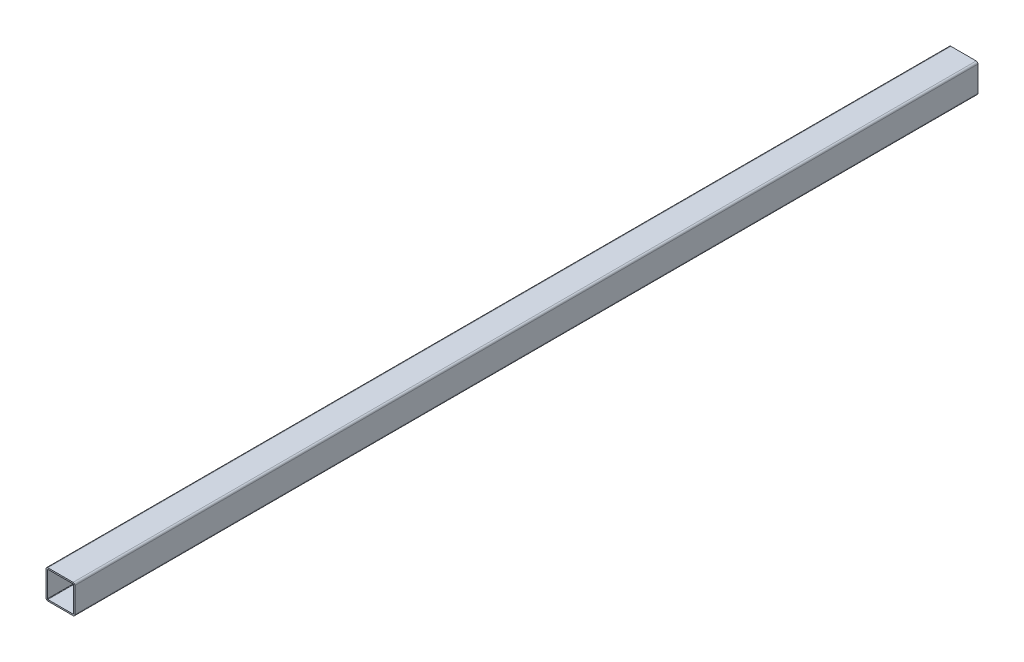
SolidWorks part; units mm, degrees
material "AISI 1010 Steel, hot rolled bar"
ref_plane "Front Plane" through (0, 0, 0) normal (0, 0, 1) x (1, 0, 0)
ref_plane "Top Plane" through (0, 0, 0) normal (0, 1, 0) x (1, 0, 0)
ref_plane "Right Plane" through (0, 0, 0) normal (1, 0, 0) x (0, 0, -1)
sketch "Sketch1" plane through (0, 0, 0) normal (0, 0, 1) x (1, 0, 0)
  line L0 (-14, 14.48) -> (14, 14.48)
  line L1 (-14, -16) -> (14, -16)
  line L2 (-16, -14) -> (-16, 14)
  line L3 (-14, 16) -> (14, 16)
  line L4 (16, -14) -> (16, 14)
  line L5 (-16, -16) -> (16, 16) construction
  line L6 (-16, 16) -> (16, -16) construction
  line L7 (14.48, -14) -> (14.48, 14)
  line L8 (-14, -14.48) -> (14, -14.48)
  line L9 (-14.48, -14) -> (-14.48, 14)
  arc A0 (14, -16) -> (16, -14) centre (14, -14) ccw
  arc A1 (-16, 14) -> (-14, 16) centre (-14, 14) cw
  arc A2 (-16, -14) -> (-14, -16) centre (-14, -14) ccw
  arc A3 (16, 14) -> (14, 16) centre (14, 14) ccw
  arc A4 (14.48, 14) -> (14, 14.48) centre (14, 14) ccw
  arc A5 (14, -14.48) -> (14.48, -14) centre (14, -14) ccw
  arc A6 (-14.48, -14) -> (-14, -14.48) centre (-14, -14) ccw
  arc A7 (-14.48, 14) -> (-14, 14.48) centre (-14, 14) cw
  point P0 (0, 0)
  dimension "D3" = 2
  dimension "D1" = 32
  dimension "D2" = 32
  dimension "D4" = 1.52
extrude "Boss-Extrude1" add sketch "Sketch1" along normal blind 500 and the other way blind 500
